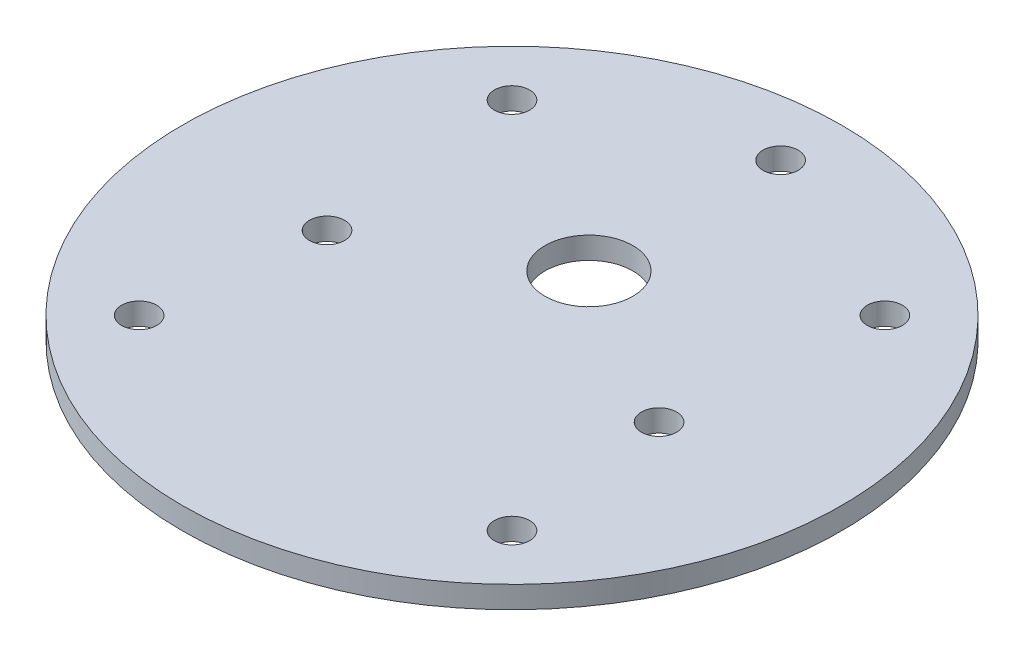
SolidWorks part; units mm, degrees
ref_plane "前视基准面" through (0, 0, 0) normal (0, 0, 1) x (1, 0, 0)
ref_plane "上视基准面" through (0, 0, 0) normal (0, 1, 0) x (1, 0, 0)
ref_plane "右视基准面" through (0, 0, 0) normal (1, 0, 0) x (0, 0, -1)
sketch "草图1" plane through (0, 0, 0) normal (0, 1, 0) x (1, 0, 0)
  line L0 (0, 0) -> (21.2132, -21.2132) construction
  line L1 (0, 0) -> (30, 0) construction
  circle A0 centre (0, 0) radius 30
  circle A3 centre (0, 7) radius 4
  circle A12 centre (16.9706, -16.9706) radius 1.6
  circle A13 centre (-16.9706, -16.9706) radius 1.6
  circle A14 centre (-16.9706, 16.9706) radius 1.6
  circle A15 centre (16.9706, 16.9706) radius 1.6
  circle A16 centre (0, 24.45) radius 1.6
  circle A17 centre (15.1121, -1.725) radius 1.6
  circle A18 centre (-15.1121, -1.725) radius 1.6
  point P5 (0, 24.45)
  point P21 (0, 7)
  dimension "D1" = 3.2
  dimension "D2" = 60
  dimension "D3" = 8
  dimension "D6" = 3.2
  dimension "D5" = 45
  dimension "D7" = 6
  dimension "D8" = 4
  dimension "D4" = 3
extrude "凸台-拉伸1" add sketch "草图1" along normal blind 2
